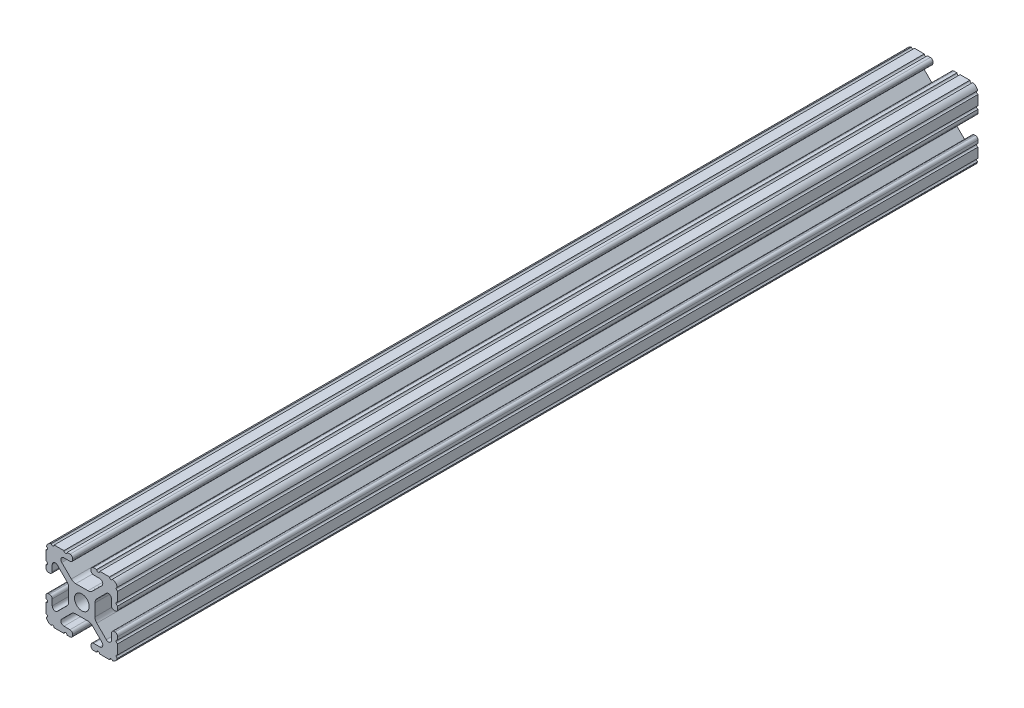
SolidWorks part; units mm, degrees
ref_plane "Front Plane" through (0, 0, 0) normal (0, 0, 1) x (1, 0, 0)
ref_plane "Top Plane" through (0, 0, 0) normal (0, 1, 0) x (1, 0, 0)
ref_plane "Right Plane" through (0, 0, 0) normal (1, 0, 0) x (0, 0, -1)
sketch "Sketch2" plane through (0, 0, 0) normal (0, 0, 1) x (1, 0, 0)
  line L0 (0, 12.7) -> (0, -12.7) construction
  line L1 (-12.7, 0) -> (12.7, 0) construction
  line L2 (3.2512, -12.7) -> (12.7, -12.7)
  line L3 (12.7, -12.7) -> (12.7, -3.2512)
  line L4 (3.2512, -12.7) -> (3.2512, -10.4902)
  line L5 (3.2512, -10.4902) -> (8.9276, -10.4902)
  line L6 (8.9276, -10.4902) -> (3.0856, -4.6482)
  line L7 (0, 0) -> (12.7, -12.7) construction
  line L8 (12.7, -3.2512) -> (10.4902, -3.2512)
  line L9 (10.4902, -3.2512) -> (10.4902, -8.9276)
  line L10 (10.4902, -8.9276) -> (4.6482, -3.0856)
  circle A0 centre (0, 0) radius 2.6035
  arc A1 (6.3485, -10.4902) -> (7.1039, -8.6665) centre (6.3485, -9.4219) ccw construction
  point P8 (0, -4.6482)
  dimension "Center Hole Diameter" = 5.207
  dimension "Rail Height" = 25.4
  dimension "Rail Width" = 25.4
  dimension "T-Slot Width" = 6.5024
  dimension "Slot Inner Width" = 14.8336
  dimension "Thickness" = 2.2098
  dimension "Slot Depth" = 5.842
  dimension "D1" = 2.2098
sketch "Sketch3" plane through (0, 0, 0) normal (1, 0, 0) x (0, 0, -1)
  line L0 (-152.4, -12.7) -> (152.4, -12.7) construction
  line L1 (-127, 0) -> (127, 0) construction
  dimension "Length" = 304.8
  dimension "D1" = 25.4
sketch "Sketch4" plane through (0, 0, 0) normal (0, 0, 1) x (1, 0, 0)
  line L0 (4.1904, -12.7) -> (10.1173, -12.7)
  line L1 (3.2512, -12.7) -> (12.7, -12.7) construction
  line L2 (3.2512, -12.7) -> (3.2512, -10.4902) construction
  line L3 (3.2512, -10.4902) -> (8.9276, -10.4902) construction
  line L4 (3.2512, -11.4294) -> (3.2512, -11.7608)
  line L5 (4.1904, -10.4902) -> (6.3485, -10.4902)
  line L6 (0, -4.6482) -> (2.164, -4.6482)
  line L7 (8.9276, -10.4902) -> (3.0856, -4.6482) construction
  line L8 (3.7373, -5.2999) -> (7.1039, -8.6665)
  line L9 (12.7, -12.7) -> (12.7, -3.2512) construction
  line L10 (10.4902, -8.9276) -> (4.6482, -3.0856) construction
  line L11 (10.4902, -3.2512) -> (10.4902, -8.9276) construction
  line L12 (10.4902, -6.3485) -> (10.4902, -4.1904)
  line L13 (12.7, -3.2512) -> (10.4902, -3.2512) construction
  line L14 (11.4294, -3.2512) -> (11.7608, -3.2512)
  line L15 (12.7, -4.1904) -> (12.7, -10.1173)
  line L16 (8.6665, -7.1039) -> (5.2999, -3.7373)
  line L17 (4.6482, 0) -> (4.6482, -2.164)
  line L18 (-12.7, 0) -> (12.7, 0) construction
  line L19 (0, -4.6482) -> (0, -2.6035)
  line L20 (0, 12.7) -> (0, -12.7) construction
  line L21 (4.6482, 0) -> (2.6035, 0)
  arc A0 (3.2512, -11.7608) -> (4.1904, -12.7) centre (4.1904, -11.7608) ccw
  arc A2 (3.2512, -11.4294) -> (4.1904, -10.4902) centre (4.1904, -11.4294) cw
  arc A3 (6.3485, -10.4902) -> (7.1039, -8.6665) centre (6.3485, -9.4219) ccw
  arc A4 (2.164, -4.6482) -> (3.7373, -5.2999) centre (2.164, -6.8732) cw
  arc A5 (10.1173, -12.7) -> (12.7, -10.1173) centre (10.1173, -10.1173) ccw
  arc A6 (8.6665, -7.1039) -> (10.4902, -6.3485) centre (9.4219, -6.3485) ccw
  arc A7 (10.4902, -4.1904) -> (11.4294, -3.2512) centre (11.4294, -4.1904) cw
  arc A8 (11.7608, -3.2512) -> (12.7, -4.1904) centre (11.7608, -4.1904) cw
  arc A9 (5.2999, -3.7373) -> (4.6482, -2.164) centre (6.8732, -2.164) cw
  circle A10 centre (0, 0) radius 2.6035 construction
  arc A11 (0, -2.6035) -> (2.6035, 0) centre (0, 0) ccw
  dimension "D1" = 2.5827
  dimension "D2" = 2.225
  dimension "D3" = 0.9392
extrude "Boss-Extrude1" add sketch "Sketch4" along normal mid plane 304.8
sketch "Sketch5" plane through (0, 0, 0) normal (0, 0, 1) x (1, 0, 0)
  line L0 (3.2512, -12.7) -> (12.7, -12.7) construction
  line L1 (4.1904, -10.4902) -> (6.3485, -10.4902) construction
  line L3 (0, 0) -> (12.7, -12.7) construction
  line L4 (6.3485, -10.4902) -> (6.3485, -12.7) construction
  line L5 (8.9276, -10.4902) -> (3.0856, -4.6482) construction
  circle A0 centre (10.3562, -12.7) radius 0.5524
  circle A1 centre (5.796, -12.7) radius 0.5524
  circle A2 centre (12.7, -10.3562) radius 0.5524
  circle A3 centre (12.7, -5.796) radius 0.5524
  point P10 (5.2694, -10.4902)
  point P12 (9.4219, -6.3485)
  dimension "D1" = 1.1049
extrude "Cut-Extrude1" cut sketch "Sketch5" against normal through all both and the other way through all
mirror "Mirror1" about plane through (0, 0, 0) normal (1, 0, 0) of bodies 137 134
mirror "Mirror2" about plane through (0, 0, 0) normal (0, 1, 0) of bodies 135
equation "\"D1@Boss-Extrude1\"=\"Length@Sketch3\""
equation "\"D1@Sketch2\"=\"Thickness@Sketch2\""
equation "\"D2@Sketch4\"=\"Slot Inner Width@Sketch2\"*0.15"
equation "\"D1@Sketch4\"=\"D3@Sketch4\"*2.75"
equation "\"D3@Sketch4\"=\"Thickness@Sketch2\"*0.425"
equation "\"D1@Sketch5\"=\"Thickness@Sketch2\"*0.5"
